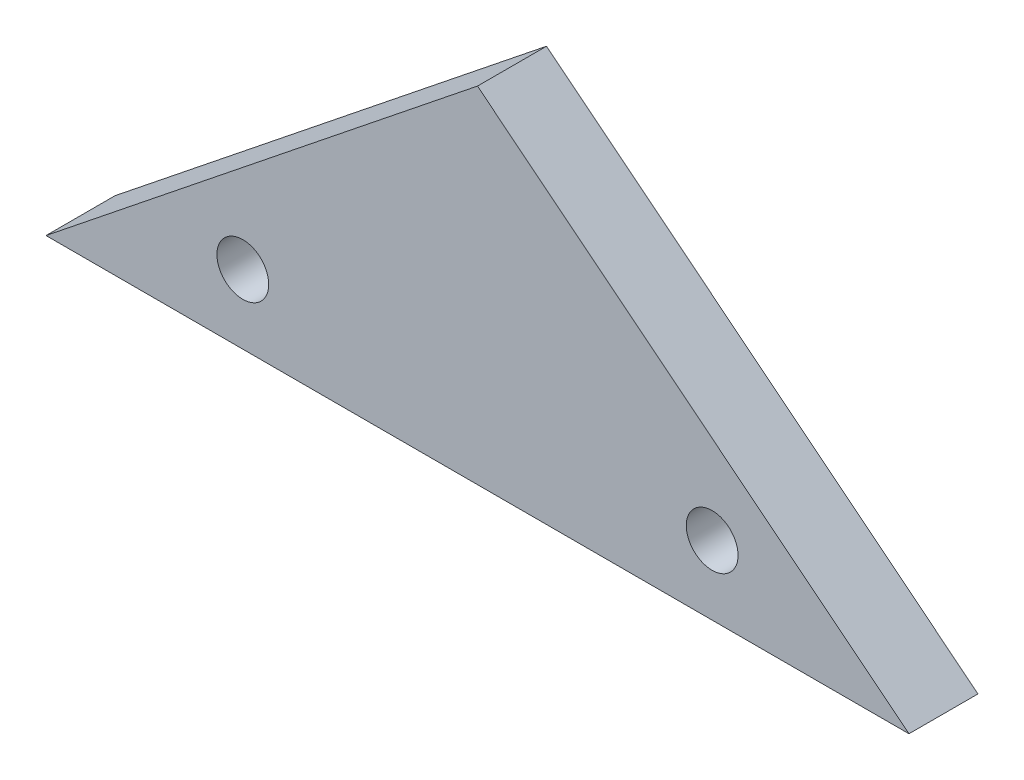
SolidWorks part; units mm, degrees
material "ABS"
ref_plane "Front" through (0, 0, 0) normal (0, 0, 1) x (1, 0, 0)
ref_plane "Top" through (0, 0, 0) normal (0, 1, 0) x (1, 0, 0)
ref_plane "Right" through (0, 0, 0) normal (1, 0, 0) x (0, 0, -1)
sketch "Sketch1" plane through (0, 0, 0) normal (0, 0, 1) x (1, 0, 0)
  line L0 (0, 0) -> (63.5, 0)
  line L1 (63.5, 0) -> (31.75, 25.4)
  line L2 (31.75, 25.4) -> (0, 0)
  point P6 (31.75, 0)
  dimension "D1" = 63.5
  dimension "D2" = 25.4
extrude "Boss-Extrude1" add sketch "Sketch1" along normal blind 5.08
sketch "Sketch2" plane through (0, 0, 5.08) normal (0, 0, 1) x (1, 0, 0)
  line L0 (0, 0) -> (63.5, 0) construction
  line L1 (31.75, 25.4) -> (0, 0) construction
  line L2 (63.5, 0) -> (31.75, 25.4) construction
  circle A0 centre (14.482, 5.08) radius 1.905
  circle A1 centre (49.018, 5.08) radius 1.905
  dimension "D1" = 3.81
  dimension "D2" = 5.08
  dimension "D3" = 5.08
  dimension "D4" = 5.08
extrude "Cut-Extrude1" cut sketch "Sketch2" against normal through all
sketch "Sketch3" plane through (0, 0, 0) normal (0, -1, 0) x (-1, 0, 0)
  line L0 (0, 0) -> (-63.5, 0) construction
  point P0 (-31.75, 0)
